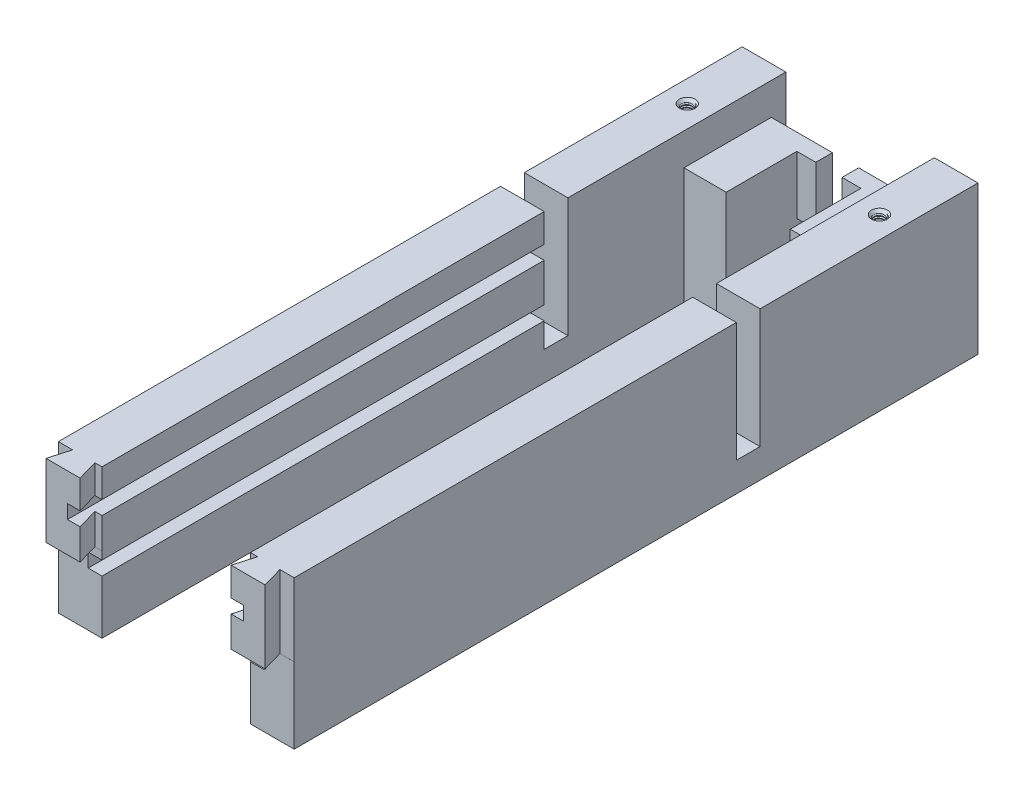
SolidWorks part; units mm, degrees
ref_plane "Front Plane" through (0, 0, 0) normal (0, 0, 1) x (1, 0, 0)
ref_plane "Top Plane" through (0, 0, 0) normal (0, 1, 0) x (1, 0, 0)
ref_plane "Right Plane" through (0, 0, 0) normal (1, 0, 0) x (0, 0, -1)
sketch "Sketch1" plane through (0, 0, 0) normal (1, 0, 0) x (0, 0, -1)
  line L1 (-64.5621, 30.5573) -> (177.4379, 30.5573)
  line L2 (-64.5621, 30.5573) -> (-64.5621, -20.4427)
  line L3 (-64.5621, -20.4427) -> (177.4379, -20.4427)
  line L4 (177.4379, 30.5573) -> (177.4379, -20.4427)
  dimension "D1" = 242
  dimension "D2" = 51
extrude "Boss-Extrude1" add sketch "Sketch1" along normal blind 15 contours L2 L3 L4 L1
sketch "Sketch26" plane through (0, 0, 0) normal (-1, 0, 0) x (0, 0, 1)
  line L1 (-172.4379, 19.5573) -> (-142.4379, 19.5573)
  line L2 (-172.4379, 19.5573) -> (-172.4379, -20.4427)
  line L3 (-172.4379, -20.4427) -> (-142.4379, -20.4427)
  line L4 (-142.4379, 19.5573) -> (-142.4379, -20.4427)
  line L5 (64.5621, -20.4427) -> (-177.4379, -20.4427) construction
  line L6 (-177.4379, 30.5573) -> (-177.4379, -20.4427) construction
  dimension "D1" = 5
  dimension "D2" = 30
  dimension "D3" = 40
extrude "Boss-Extrude3" add sketch "Sketch26" against normal blind 29.5
sketch "Sketch28" plane through (29.5, 0, 0) normal (1, 0, 0) x (0, 0, -1)
  line L0 (147.0417, -20.4427) -> (147.0417, -10.6927)
  line L1 (172.4379, -20.4427) -> (142.4379, -20.4427) construction
  line L2 (147.0417, -10.6927) -> (162.0417, -10.6927)
  line L3 (162.0417, -10.6927) -> (162.0417, -20.4427)
  line L4 (162.0417, -20.4427) -> (147.0417, -20.4427)
  dimension "D1" = 9.75
  dimension "D2" = 15
extrude "Boss-Extrude5" add sketch "Sketch28" along normal blind 4.5
sketch "Sketch29" plane through (29.5, 0, 0) normal (1, 0, 0) x (0, 0, -1)
  line L0 (172.4379, 19.5573) -> (166.7379, 19.5573)
  line L1 (142.4379, 19.5573) -> (172.4379, 19.5573) construction
  line L2 (166.7379, 19.5573) -> (166.7379, -0.4427)
  line L3 (166.7379, -0.4427) -> (172.4379, -0.4427)
  line L4 (172.4379, 19.5573) -> (172.4379, -20.4427) construction
  line L5 (172.4379, -0.4427) -> (172.4379, 19.5573)
  dimension "D1" = 20
  dimension "D2" = 5.7
extrude "Boss-Extrude6" add sketch "Sketch29" along normal blind 6.5
sketch "Sketch12" plane through (0, 30.5573, 0) normal (0, 1, 0) x (1, 0, 0)
  line L0 (0, -57.4487) -> (4.9097, -57.4487)
  line L1 (0, -64.5621) -> (0, 177.4379) construction
  line L2 (4.9097, -57.4487) -> (2.87, -64.5621)
  line L3 (15, -64.5621) -> (0, -64.5621) construction
  line L4 (2.87, -64.5621) -> (0, -64.5621)
  line L5 (0, -64.5621) -> (0, -57.4487)
  line L6 (15, -57.4487) -> (15, -64.5621)
  line L7 (15, -64.5621) -> (15, 177.4379) construction
  line L8 (15, -64.5621) -> (14.57, -64.5621)
  line L9 (14.57, -64.5621) -> (12.5303, -57.4487)
  line L10 (12.5303, -57.4487) -> (15, -57.4487)
  dimension "D1" = 7.4
  dimension "D2" = 7.4
  dimension "D3" = 106
  dimension "D4" = 106
  dimension "D5" = 11.7
  dimension "D6" = 2.87
extrude "Cut-Extrude8" cut sketch "Sketch12" against normal blind 25
sketch "Sketch13" plane through (0, -20.4427, 0) normal (0, -1, 0) x (1, 0, 0)
  line L0 (15, 64.5621) -> (15, -142.4379) construction
  line L1 (0, 64.5621) -> (15, 64.5621)
  line L2 (0, 64.5621) -> (0, 57.4521)
  line L3 (0, 57.4521) -> (15, 57.4521)
  line L4 (15, 64.5621) -> (15, 57.4521)
  dimension "D1" = 7.11
extrude "Cut-Extrude9" cut sketch "Sketch13" against normal blind 26
sketch "Sketch17" plane through (0, 30.5573, 0) normal (0, 1, 0) x (1, 0, 0)
  line L0 (15, -57.4487) -> (15, 177.4379) construction
  line L1 (0, 110.4379) -> (15, 110.4379)
  line L2 (0, 110.4379) -> (0, 102.5879)
  line L3 (0, 102.5879) -> (15, 102.5879)
  line L4 (15, 110.4379) -> (15, 102.5879)
  line L6 (0, 102.5879) -> (15, 102.5879)
  line L7 (0, 102.5879) -> (0, 94.4379)
  line L8 (0, 94.4379) -> (15, 94.4379)
  line L9 (15, 102.5879) -> (15, 94.4379)
  line M14 (15, -57.4487) -> (15, 177.4379)
  line M16 (0, 177.4379) -> (0, -57.4487)
  dimension "D1" = 7.85
  dimension "D2" = 8.15
extrude "Cut-Extrude10" cut sketch "Sketch17" against normal blind 41 contours L8 L3 M16 M14 region at (7.5, 30.5573, -98.5129)
sketch "Sketch7" plane through (0, 0, -94.4379) normal (0, 0, -1) x (-1, 0, 0)
  line L0 (-15, -20.4427) -> (-15, -1.9427)
  line L1 (-15, 2.8073) -> (-15, 16.0573)
  line L2 (-10.25, 2.8073) -> (-15, 2.8073)
  line L3 (-10.25, 2.8073) -> (-10.25, -1.9427)
  line L4 (-10.25, -1.9427) -> (-15, -1.9427)
  line L5 (-15, 2.8073) -> (-15, -1.9427)
  line L6 (-15, 30.5573) -> (-15, -20.4427) construction
  line L8 (-15, 16.0573) -> (-10.25, 16.0573)
  line L9 (-15, 16.0573) -> (-15, 20.8073)
  line L10 (-15, 20.8073) -> (-10.25, 20.8073)
  line L11 (-10.25, 16.0573) -> (-10.25, 20.8073)
  dimension "D1" = 18.5
  dimension "D2" = 4.75
  dimension "D3" = 4.75
  dimension "D4" = 13.25
  dimension "D5" = 4.75
  dimension "D6" = 4.75
extrude "Cut-Extrude5" cut sketch "Sketch7" against normal blind 165 contours L4 L3 L2 | L9 L8 L11 L10 region at (12.625, 0.4323, -94.4379)
sketch "Sketch22" plane through (0, 30.5573, 0) normal (0, 1, 0) x (1, 0, 0)
  line L0 (15, 177.4379) -> (15, 161.9379)
  line L1 (15, 102.5879) -> (15, 177.4379) construction
  line L3 (15, 161.9379) -> (8, 161.9379)
  line L4 (15, 161.9379) -> (15, 158.7879)
  line L5 (15, 158.7879) -> (8, 158.7879)
  line L6 (8, 161.9379) -> (8, 158.7879)
  line M5 (15, 102.5879) -> (15, 177.4379)
  dimension "D1" = 15.5
  dimension "D2" = 7
  dimension "D3" = 3.15
extrude "Cut-Extrude13" [suppressed] cut sketch "Sketch22" against normal blind 45 contours L3 L6 L5 M5
ref_plane "Plane1" through (40.5, 0, 0) normal (1, 0, 0) x (0, 0, -1)
sketch "Sketch18" [suppressed] plane through (0, 30.5573, 0) normal (0, 1, 0) x (1, 0, 0)
  line L0 (15, 102.5879) -> (15, 136.5879)
  line L1 (15, 102.5879) -> (15, 177.4379) construction
  line L3 (15, 136.5879) -> (10, 136.5879)
  line L4 (15, 136.5879) -> (15, 144.0879)
  line L5 (15, 144.0879) -> (10, 144.0879)
  line L6 (10, 136.5879) -> (10, 144.0879)
  line M6 (15, 102.5879) -> (15, 177.4379)
  dimension "D1" = 34
  dimension "D2" = 5
  dimension "D3" = 7.5
extrude "Cut-Extrude11" [suppressed] cut sketch "Sketch18" against normal blind 38 contours L6 L3 L5 M6
sketch "Sketch23" [suppressed] plane through (0, 0, -177.4379) normal (0, 0, -1) x (-1, 0, 0)
  line L0 (-15, -20.4427) -> (-15, 9.0573)
  line L1 (-15, 30.5573) -> (-15, -20.4427) construction
  line L3 (-15, 9.0573) -> (-10.5, 9.0573)
  line L4 (-15, 9.0573) -> (-15, 13.5573)
  line L5 (-15, 13.5573) -> (-10.5, 13.5573)
  line L6 (-10.5, 9.0573) -> (-10.5, 13.5573)
  line M5 (-15, 30.5573) -> (-15, -20.4427)
  dimension "D1" = 4.5
  dimension "D2" = 4.5
  dimension "D3" = 29.5
extrude "Cut-Extrude14" [suppressed] cut sketch "Sketch23" against normal blind 45 contours L3 L6 L5 M5
mirror "Mirror4" about plane through (40.5, 0, 0) normal (1, 0, 0) of bodies 107 113
sketch "Sketch30" plane through (0, 30.5573, 0) normal (0, 1, 0) x (1, 0, 0)
  circle A0 centre (73.5, 151.0787) radius 2
  circle A1 centre (7.5, 151.0787) radius 2
hole_wizard "#8-32 Tapped Hole1" positions "Sketch35" profile "Sketch37" tap size "#8-32" standard "ANSI Inch"
sketch "Sketch35" plane through (0, 30.5573, 0) normal (0, 1, 0) x (1, 0, 0)
  point P0 (7.5, 151.0787)
  point P3 (73.5, 151.0787)
sketch "Sketch37" plane through (7.5, 30.5573, -151.0787) normal (1, 0, 0) x (0, 0, 1)
  line L0 (0, 0) -> (0, 10.7074)
  line L1 (0, 10.7074) -> (1.7272, 9.6696)
  line L2 (1.7272, 9.6696) -> (1.7272, 0.9906)
  line L3 (1.7272, 0.9906) -> (2.7178, 0)
  line L5 (2.7178, 0) -> (0, 0)
  line L6 (-1.7272, 0.9906) -> (-2.7178, 0) construction
  line L10 (0, 10.7074) -> (-1.7272, 9.6696) construction
  line L11 (0, -6.35) -> (0, 107.95) construction
  dimension "Tap Drill Dia." = 3.4544
  dimension "Tap Drill Depth" = 10.7074
  dimension "Near C'Sink Dia." = 5.4356
  dimension "Near C'Sink Angle" = 90
  dimension "Drill Angle" = 118
cosmetic thread "Hole Thread1" parameters "D1"=8.33, "D2"=4.1656
cosmetic thread "Hole Thread2" parameters "D1"=8.33, "D2"=4.1656
thread "Thread3" pitch 0.7937 method cut profile "Thread Profile5" start angle 0, offset 1, length 10, pitch 0.7937, diameter 3.4544
ref_plane "Plane6" through (5.7728, 30.5667, -151.0787) normal (0, 0, 1) x (-1, 0, 0)
sketch "Thread Profile5" plane through (5.7728, 30.5667, -151.0787) normal (0, 0, 1) x (-1, 0, 0)
  line L0 (0, 0) -> (0, 0.7937) construction
  line L1 (0, 0) -> (0.4296, 0.248)
  line L2 (0.4296, 0.248) -> (0.4296, 0.3473)
  line L3 (0.4296, 0.3473) -> (0, 0.5953)
  line L4 (0.4296, 0.2977) -> (0, 0.2977) construction
  line L11 (0, 0) -> (0, 0.5953)
  point P2 (0, 0)
  dimension "Pitch" = 0.7937
  dimension "Profile_Angle" = 60
  dimension "Profile_Land" = 0.0992
  dimension "Profile_Height" = 0.4296
thread "Thread4" pitch 0.7937 method cut profile "Thread Profile6" start angle 0, offset 1, length 10, pitch 0.7937, diameter 3.4544
ref_plane "Plane7" through (71.7728, 30.5667, -151.0787) normal (0, 0, 1) x (-1, 0, 0)
sketch "Thread Profile6" plane through (71.7728, 30.5667, -151.0787) normal (0, 0, 1) x (-1, 0, 0)
  line L0 (0, 0) -> (0, 0.7937) construction
  line L1 (0, 0) -> (0.4296, 0.248)
  line L2 (0.4296, 0.248) -> (0.4296, 0.3473)
  line L3 (0.4296, 0.3473) -> (0, 0.5953)
  line L4 (0.4296, 0.2977) -> (0, 0.2977) construction
  line L11 (0, 0) -> (0, 0.5953)
  point P2 (0, 0)
  dimension "Pitch" = 0.7937
  dimension "Profile_Angle" = 60
  dimension "Profile_Land" = 0.0992
  dimension "Profile_Height" = 0.4296
